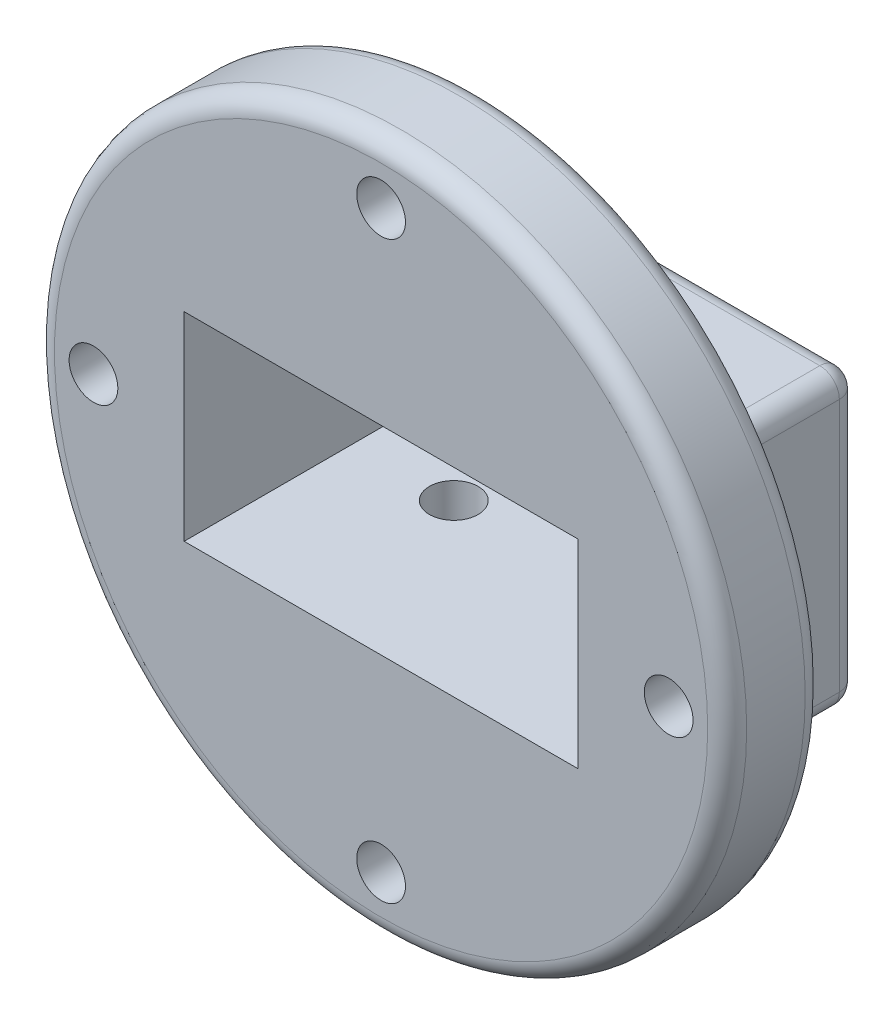
SolidWorks part; units mm, degrees
ref_plane "前视基准面" through (0, 0, 0) normal (0, 0, 1) x (1, 0, 0)
ref_plane "上视基准面" through (0, 0, 0) normal (0, 1, 0) x (1, 0, 0)
ref_plane "右视基准面" through (0, 0, 0) normal (1, 0, 0) x (0, 0, -1)
sketch "草图1" plane through (0, 0, 0) normal (0, 0, 1) x (1, 0, 0)
  line L0 (0, 0) -> (-20.2, 0)
  line L1 (-20.2, 0) -> (-20.2, 10.2)
  line L2 (-20.2, 10.2) -> (20.2, 10.2)
  line L3 (20.2, 10.2) -> (20.2, -10.2)
  line L4 (20.2, -10.2) -> (-20.2, -10.2)
  line L5 (-20.2, -10.2) -> (-20.2, 0)
  line L6 (0, 0) -> (20.2, 0)
  line L7 (0, 0) -> (0, 10.2)
  line L8 (0, 15) -> (24, 15)
  line L9 (24, 15) -> (24, -15)
  line L10 (24, -15) -> (-24, -15)
  line L11 (-24, -15) -> (-24, 15)
  line L12 (-24, 15) -> (0, 15)
  circle A0 centre (0, 0) radius 29.5
  circle A1 centre (0, 29.5) radius 2.5
  circle A2 centre (29.5, 0) radius 2.5
  circle A3 centre (0, -29.5) radius 2.5
  circle A4 centre (-29.5, 0) radius 2.5
  circle A5 centre (0, 0) radius 23.5
  circle A6 centre (0, 0) radius 35.5
  point P14 (0, 0)
  dimension "D1" = 4
extrude "凸台-拉伸1" add sketch "草图1" along normal blind 10 contours A6 | A6 | A6 A3 A0 A4 A1 A2 | A5 A3 A0 A2 A1 A4 | A6 | A5 L10 L9 L8 | L8 A5 L12 | L12 A5 L10 L8 L4 L5 L1 L2 L3 | A5 L12 L11 L10 | L10 A5 region at (0, 18.4589, 0) region at (9.045, 14.4424, 0) region at (21.045, 14.6942, 0) region at (-23.8058, 0, 0) region at (0, -18.4589, 0) region at (26.1686, 0, 0) region at (-34.4959, 0, 0)
extrude "凸台-拉伸2" add sketch "草图1<5>" against normal blind 15 contours L12 A5 L10 L8 L4 L5 L1 L2 L3 | A5 L10 L9 L8 | A5 L12 L11 L10 region at (9.045, 14.4424, 0) region at (21.045, 14.6942, 0) region at (-23.8058, 0, 0)
sketch "草图1<5>" plane through (0, 0, 0) normal (0, 0, 1) x (1, 0, 0) same geometry as "草图1"
fillet "圆角1" radius 2 16 edges at (24, 0, 0) (24, 15, -7.5) (0, 15, 0) (24, 0, -15) (0, 15, -15) (-20.2, 0, -15) (0, 10.2, -15) (20.2, 0, -15) (0, -10.2, -15) (-24, 0, -15) (-24, 15, -7.5) (-24, 0, 0) (24, -15, -7.5) (0, -15, -15) (-24, -15, -7.5) (0, -15, 0)
sketch "草图3" plane through (0, 15, 0) normal (0, 1, 0) x (1, 0, 0)
  line L0 (0, 14.9558) -> (0, 7.4558)
  line L1 (0, 7.4558) -> (10, 7.4558)
  circle A0 centre (10, 7.4558) radius 2.5
  circle A1 centre (-10, 7.4558) radius 2.5
extrude "切除-拉伸1" cut sketch "草图3" against normal through all contours A1 | A0 region at (10, 15, -5.0265) region at (-10, 15, -7.4558)
fillet "圆角2" radius 2 2 edges at (35.5, 0, 0) (35.5, 0, 10)
